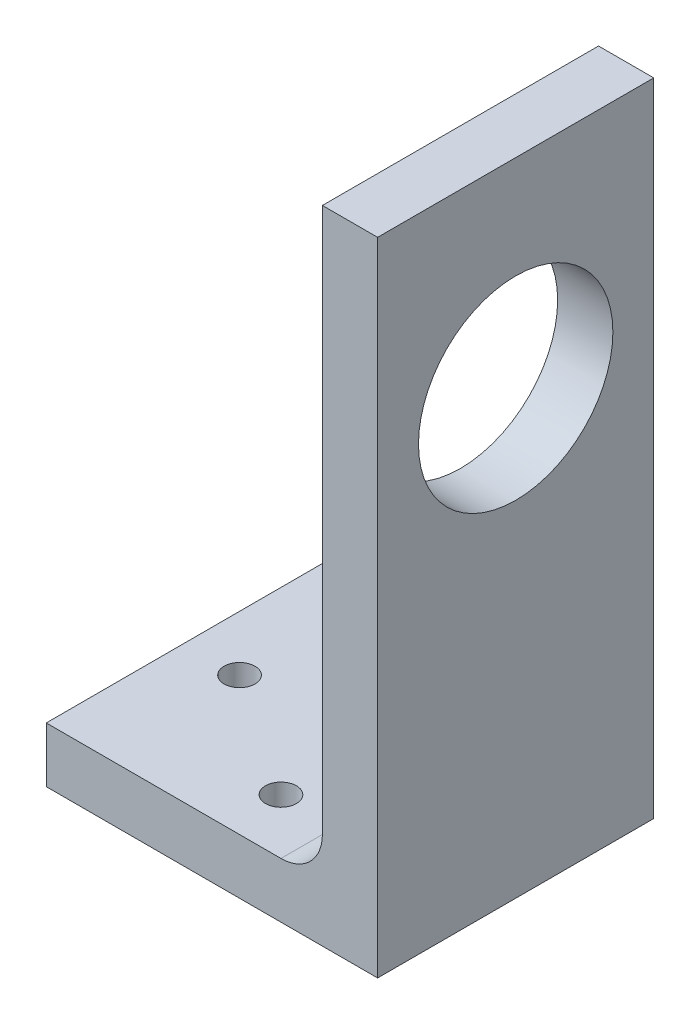
SolidWorks part; units mm, degrees
ref_plane "Front Plane" through (0, 0, 0) normal (0, 0, 1) x (1, 0, 0)
ref_plane "Top Plane" through (0, 0, 0) normal (0, 1, 0) x (1, 0, 0)
ref_plane "Right Plane" through (0, 0, 0) normal (1, 0, 0) x (0, 0, -1)
sketch "Sketch3" plane through (0, 0, 0) normal (1, 0, 0) x (0, 0, -1)
  line L0 (5.748, 54.704) -> (26.002, 13.55) construction
  line L1 (0, 0) -> (31.75, 0)
  line L2 (0, 0) -> (0, 67.404)
  line L3 (0, 67.404) -> (31.75, 67.404)
  line L4 (31.75, 0) -> (31.75, 67.404)
  line L5 (5.748, 54.704) -> (14.875, 54.704) construction
  line L6 (5.748, 54.704) -> (5.748, 13.55) construction
  line L7 (5.748, 13.55) -> (14.875, 13.55) construction
  line L8 (26.002, 54.704) -> (26.002, 13.55) construction
  line L9 (26.002, 54.704) -> (5.748, 13.55) construction
  line L10 (10.875, 58.427) -> (20.875, 9.827) construction
  line L11 (10.875, 9.827) -> (20.875, 58.427) construction
  line L12 (16.875, 13.55) -> (26.002, 13.55) construction
  line L13 (14.875, 13.55) -> (14.875, 6.946) construction
  line L14 (14.875, 6.946) -> (16.875, 6.946) construction
  line L15 (16.875, 13.55) -> (16.875, 6.946) construction
  line L16 (15.875, 34.127) -> (-939.9401, 34.127) construction
  line L17 (14.875, 61.308) -> (16.875, 61.308) construction
  line L18 (14.875, 54.704) -> (14.875, 61.308) construction
  line L19 (16.875, 54.704) -> (16.875, 61.308) construction
  line L20 (16.875, 54.704) -> (26.002, 54.704) construction
  circle A0 centre (10.875, 9.827) radius 2.2 construction
  circle A1 centre (20.875, 9.827) radius 2.2 construction
  circle A2 centre (10.875, 58.427) radius 2.2 construction
  circle A3 centre (20.875, 58.427) radius 2.2 construction
  circle A4 centre (15.875, 44.45) radius 11.176
  point P13 (15.875, 6.946)
  point P22 (15.875, 34.127)
  point P23 (15.875, 34.127)
  point P32 (15.875, 44.45)
  point P34 (15.875, 0)
  dimension "D3" = 4.4
  dimension "D11" = 22.352
  dimension "D1" = 10
  dimension "D2" = 48.6
  dimension "D4" = 41.154
  dimension "D5" = 20.254
  dimension "D6" = 2
  dimension "D7" = 6.604
  dimension "D8" = 30.9
  dimension "D12" = 12.7
  dimension "D9" = 44.45
  dimension "D10" = 31.75
extrude "Boss-Extrude1" add sketch "Sketch3" along normal blind 6.35
sketch "Sketch5" plane through (6.35, 0, 0) normal (1, 0, 0) x (0, 0, -1)
  line L1 (0, 0) -> (31.75, 0)
  line L2 (0, 0) -> (0, -6.35)
  line L3 (0, -6.35) -> (31.75, -6.35)
  line L4 (31.75, 0) -> (31.75, -6.35)
  dimension "D1" = 6.35
extrude "Boss-Extrude2" add sketch "Sketch5" against normal blind 38.1
fillet "Fillet1" radius 4.7625 1 edges at (0, 0, -15.875)
sketch "Sketch6" plane through (0, 0, 0) normal (0, 1, 0) x (1, 0, 0)
  line L0 (-31.75, 0) -> (-4.7625, 0) construction
  line L1 (-4.7625, 0) -> (-4.7625, 31.75) construction
  line L2 (-31.75, 31.75) -> (-31.75, 0) construction
  line L3 (0, 15.875) -> (-33.0413, 15.875) construction
  line L4 (0, 31.75) -> (0, 0) construction
  circle A0 centre (-11.1125, 6.35) radius 1.777
  circle A2 centre (-25.4, 15.875) radius 1.777
  circle A3 centre (-11.1125, 25.4) radius 1.777
  dimension "D1" = 3.554
  dimension "D2" = 6.35
  dimension "D3" = 6.35
  dimension "D4" = 6.35
extrude "Cut-Extrude1" cut sketch "Sketch6" against normal through all
equation "\"D1@Sketch6\" = 3.3mm + \"normTol\""
equation "\"tightTol\"= 0.005in"
equation "\"normTol\"= 0.01in"
equation "\"looseTol\"= 0.02in"
equation "\"D11@Sketch3\"=0.875000in+\"tightTol\""
